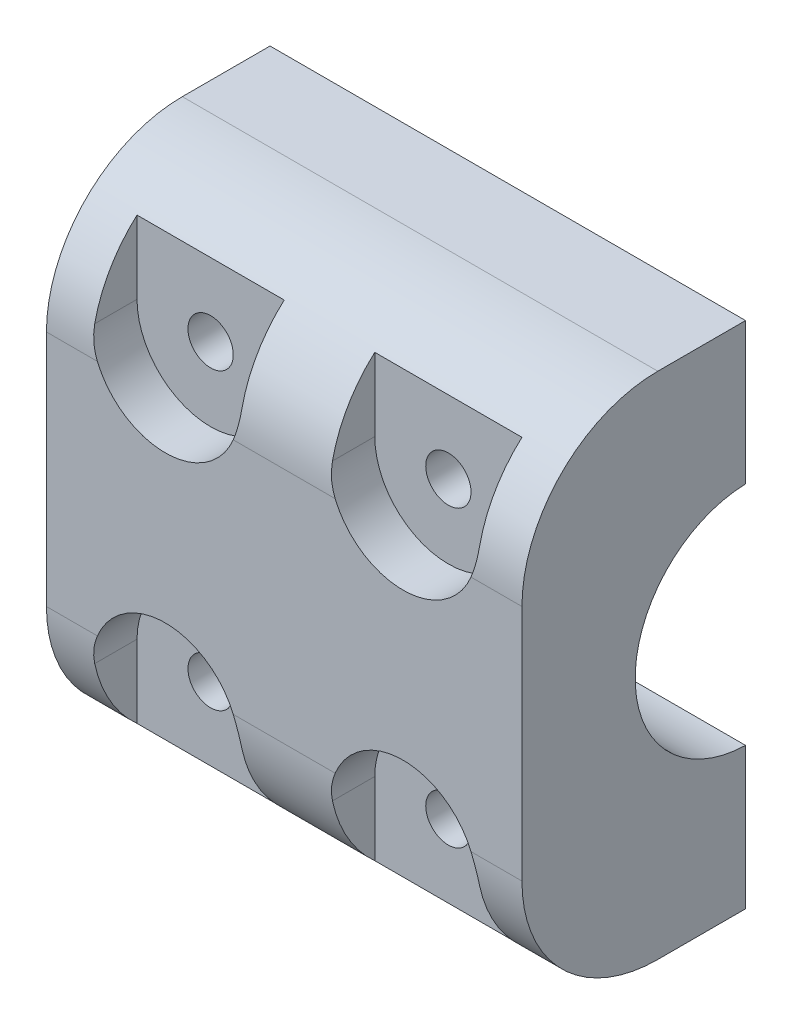
SolidWorks part; units mm, degrees
ref_plane "Front Plane" through (0, 0, 0) normal (0, 0, 1) x (1, 0, 0)
ref_plane "Top Plane" through (0, 0, 0) normal (0, 1, 0) x (1, 0, 0)
ref_plane "Right Plane" through (0, 0, 0) normal (1, 0, 0) x (0, 0, -1)
sketch "Sketch1" plane through (0, 0, 0) normal (1, 0, 0) x (0, 0, -1)
  line L0 (0, 22.5) -> (0, -22.5) construction
  line L1 (-0.25, 22.5) -> (-0.25, 9.9969)
  line L2 (-0.25, -9.9969) -> (-0.25, -22.5)
  line L4 (-0.25, 22.5) -> (-0.25, -22.5) construction
  line L6 (-20, 10.5) -> (-20, -10.5)
  line L8 (0, 22.5) -> (-3, 22.5)
  line L9 (-3, 22.5) -> (-8, 22.5)
  line L10 (0, 0) -> (-22.5, 0) construction
  line L11 (-3, -22.5) -> (-8, -22.5)
  line L12 (0, -22.5) -> (-3, -22.5)
  arc A0 (0, 22.5) -> (0, -22.5) centre (0, 0) ccw construction
  arc A1 (0, 10) -> (0, -10) centre (0, 0) ccw
  circle A3 centre (0, 0) radius 10 construction
  arc A7 (-8, 22.5) -> (-20, 10.5) centre (-8, 10.5) ccw
  arc A8 (-8, -22.5) -> (-20, -10.5) centre (-8, -10.5) cw
  dimension "D2" = 45
  dimension "D3" = 20
  dimension "D4" = 3
  dimension "D5" = 5
  dimension "D1" = 0.25
extrude "Boss-Extrude1" add sketch "Sketch1" against normal blind 42 contours A1 L1 A0 L2 region at (0, 0, 10.7608)
sketch "Sketch2" plane through (0, 0, 0.25) normal (0, 0, 1) x (1, 0, 0)
  line L0 (0, 0) -> (-42, 0) construction
  line L1 (-42, -22.5) -> (0, -22.5) construction
  line L2 (-42, 13) -> (-21, 13) construction
  line L3 (-10.5, 11) -> (-31.5, 11) construction
  line L5 (-21, 22.5) -> (-21, -22.5) construction
  line L6 (-42, 22.5) -> (-42, 10.5) construction
  line L7 (-42, 10.5) -> (-42, -10.5) construction
  line L11 (-42, 22.5) -> (0, 22.5) construction
  circle A0 centre (-31.5, 13) radius 2
  circle A1 centre (-10.5, 13) radius 2
  circle A2 centre (-10.5, -13) radius 2
  circle A3 centre (-31.5, -13) radius 2
  point P21 (-21, 11)
  dimension "D2" = 4
  dimension "D1" = 13
extrude "Cut-Extrude2" cut sketch "Sketch2" along normal through all contours A1 | A0 | A3 | A2 region at (-31.5, 13, 0.25) region at (-10.5, 13, 0.25) region at (-10.5, -13, 0.25) region at (-31.5, -13, 0.25)
sketch "Sketch3" plane through (0, 0, 20) normal (0, 0, 1) x (1, 0, 0)
  line L0 (0, 0) -> (-42, 0) construction
  line L2 (-38, 13) -> (-38, 19.5)
  line L3 (-38, 19.5) -> (-25, 19.5)
  line L4 (-25, 19.5) -> (-25, 13)
  line L5 (-17, 13) -> (-17, 19.5)
  line L6 (-17, 19.5) -> (-4, 19.5)
  line L7 (-4, 19.5) -> (-4, 13)
  line L8 (-4, -19.5) -> (-4, -13)
  line L9 (-17, -19.5) -> (-4, -19.5)
  line L10 (-17, -13) -> (-17, -19.5)
  line L11 (-25, -19.5) -> (-25, -13)
  line L12 (-38, -19.5) -> (-25, -19.5)
  line L13 (-38, -13) -> (-38, -19.5)
  line L14 (-42, 10.5) -> (-42, -10.5) construction
  arc A0 (-38, 13) -> (-25, 13) centre (-31.5, 13) ccw
  arc A1 (-17, 13) -> (-4, 13) centre (-10.5, 13) ccw
  arc A2 (-17, -13) -> (-4, -13) centre (-10.5, -13) cw
  arc A3 (-38, -13) -> (-25, -13) centre (-31.5, -13) cw
  dimension "D1" = 13
extrude "Cut-Extrude3" cut sketch "Sketch3" against normal blind 4
